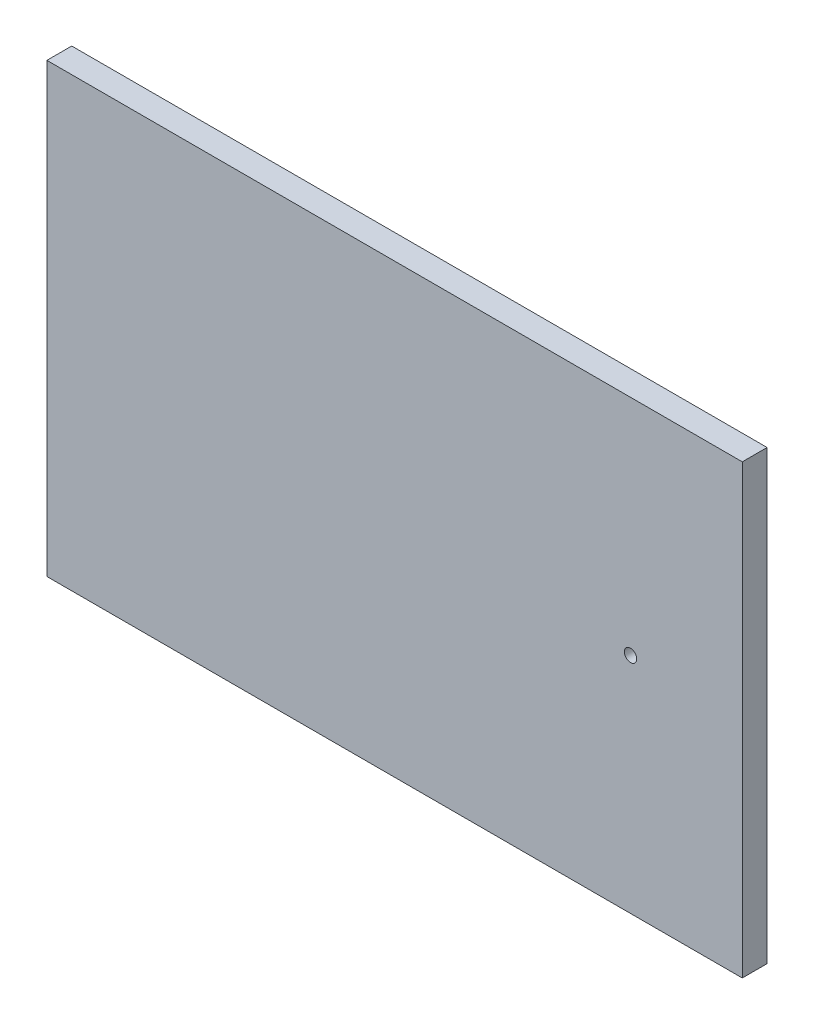
SolidWorks part; units mm, degrees
ref_plane "Front Plane" through (0, 0, 0) normal (0, 0, 1) x (1, 0, 0)
ref_plane "Top Plane" through (0, 0, 0) normal (0, 1, 0) x (1, 0, 0)
ref_plane "Right Plane" through (0, 0, 0) normal (1, 0, 0) x (0, 0, -1)
sketch "Sketch2" plane through (0, 0, 0) normal (0, 0, 1) x (1, 0, 0)
  line L1 (0, 0) -> (355.6, 0)
  line L2 (0, 0) -> (0, -228.6)
  line L3 (0, -228.6) -> (355.6, -228.6)
  line L4 (355.6, 0) -> (355.6, -228.6)
  dimension "D1" = 355.6
  dimension "D2" = 228.6
extrude "Boss-Extrude1" add sketch "Sketch2" along normal blind 12.7
sketch "Sketch3" plane through (0, 0, 12.7) normal (0, 0, 1) x (1, 0, 0)
  line L1 (355.6, -228.6) -> (355.6, 0) construction
  circle A1 centre (298.45, -114.3) radius 3.175
  dimension "D4" = 6.35
  dimension "D3" = 57.15
extrude "Cut-Extrude1" cut sketch "Sketch3" against normal blind 12.7
